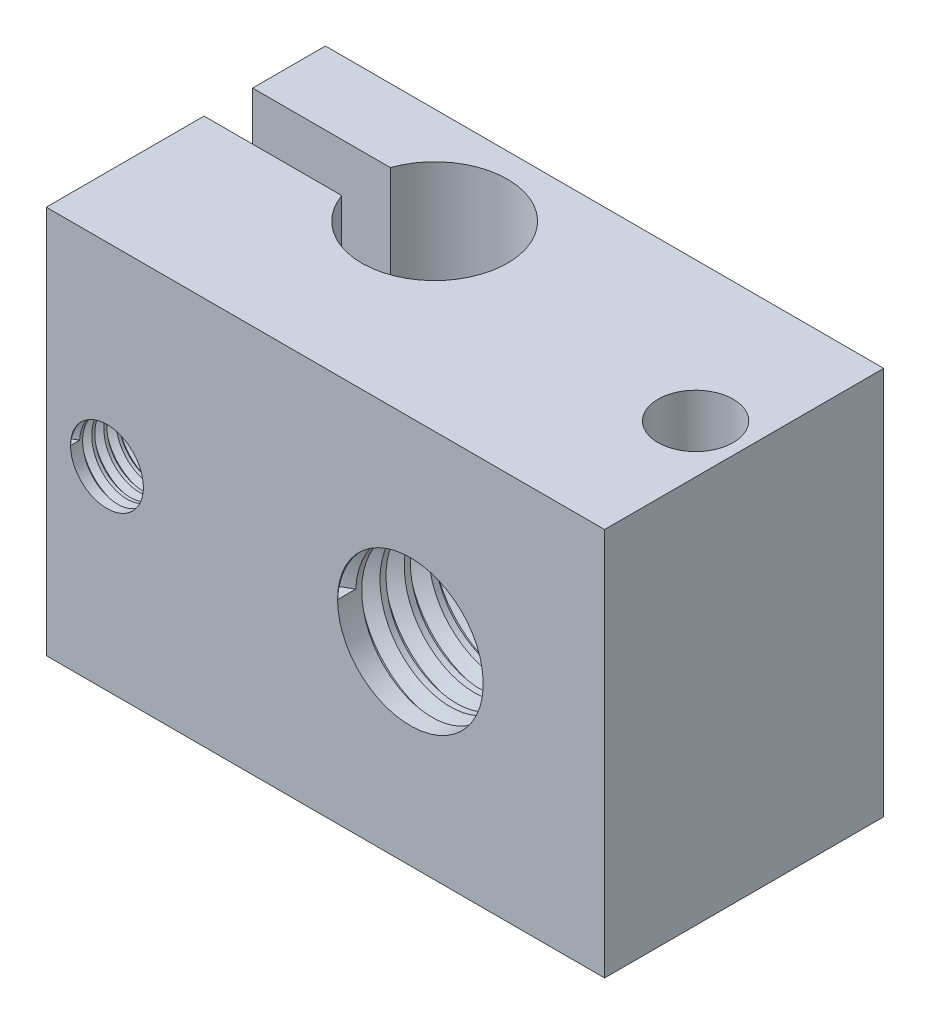
SolidWorks part; units mm, degrees
material "6061 Alloy"
ref_plane "Front Plane" through (0, 0, 0) normal (0, 0, 1) x (1, 0, 0)
ref_plane "Top Plane" through (0, 0, 0) normal (0, 1, 0) x (1, 0, 0)
ref_plane "Right Plane" through (0, 0, 0) normal (1, 0, 0) x (0, 0, -1)
sketch "Sketch1" plane through (0, 0, 0) normal (0, 0, 1) x (1, 0, 0)
  line L1 (-7, 7.0968) -> (16, 7.0968)
  line L2 (-7, 7.0968) -> (-7, -8.9032)
  line L3 (-7, -8.9032) -> (16, -8.9032)
  line L4 (16, 7.0968) -> (16, -8.9032)
  circle A0 centre (8, -0.9032) radius 3
  circle A1 centre (-4.5, -0.9032) radius 1.5
  dimension "D7" = 6
  dimension "D8" = 3
  dimension "D1" = 16
  dimension "D2" = 23
  dimension "D3" = 20.5
  dimension "D4" = 8
  dimension "D5" = 8
  dimension "D6" = 8
extrude "Boss-Extrude1" add sketch "Sketch1" along normal blind 11.5 contours L1 L4 L3 L2 | A1 | A0
sketch "Sketch10" plane through (0, -8.9032, 0) normal (0, -1, 0) x (1, 0, 0)
  line L0 (16, 11.5) -> (16, 0) construction
  line L1 (-7, 0) -> (16, 0) construction
  line L2 (-1.5, 4) -> (-7, 4) construction
  line L3 (-7, 11.5) -> (-7, 0) construction
  line L4 (-1.3284, 5) -> (-7, 5)
  line L5 (-1.3284, 3) -> (-7, 3)
  line L6 (-1.5, 5) -> (-7, 5) construction
  line L7 (-1.5, 3) -> (-7, 3) construction
  line L8 (-7, 5) -> (-7, 3)
  arc A0 (-1.3284, 3) -> (-1.3284, 5) centre (1.5, 4) ccw
  circle A1 centre (14, 5.75) radius 1.55
  dimension "D3" = 6
  dimension "D5" = 3.1
  dimension "D1" = 14.5
  dimension "D2" = 4
  dimension "D4" = 2
  dimension "D6" = 5.75
  dimension "D7" = 1
  dimension "D8" = 2
extrude "Cut-Extrude1" cut sketch "Sketch10" against normal through all
sketch "Sketch11" plane through (0, 0, 0) normal (0, 0, -1) x (-1, 0, 0)
  line L0 (-16, 7.0968) -> (-16, -8.9032) construction
  line L1 (7, -8.9032) -> (-16, -8.9032) construction
  circle A0 centre (-14, -0.9032) radius 1.5
  dimension "D3" = 3
  dimension "D1" = 2
  dimension "D2" = 8
extrude "Cut-Extrude2" cut sketch "Sketch11" against normal blind 6.025
thread "Thread1" pitch 0.5 start angle 0, offset 0, length 11.5, pitch 0.5, diameter 3
ref_plane "Plane1" through (-6, -0.9032, 11.5) normal (0, -1, 0) x (-1, 0, 0)
sketch "Thread Profile1" plane through (-6, -0.9032, 11.5) normal (0, -1, 0) x (-1, 0, 0)
  line L0 (0, 0) -> (0, 0.5) construction
  line L1 (0, 0) -> (0.2706, 0.1562)
  line L2 (0.2706, 0.1562) -> (0.2706, 0.2187)
  line L3 (0.2706, 0.2187) -> (0, 0.375)
  line L4 (0.2706, 0.1875) -> (0, 0.1875) construction
  line L11 (0, 0) -> (0, 0.375)
  point P2 (0, 0)
  dimension "Pitch" = 0.5
  dimension "Profile_Angle" = 60
  dimension "Profile_Land" = 0.0625
  dimension "Profile_Height" = 0.2706
thread "Thread2" pitch 1 profile "Thread Profile2" start angle 0, offset 0, length 11.5, pitch 1, diameter 6
ref_plane "Plane2" through (5, -0.9032, 11.5) normal (0, -1, 0) x (-1, 0, 0)
sketch "Thread Profile2" plane through (5, -0.9032, 11.5) normal (0, -1, 0) x (-1, 0, 0)
  line L0 (0, 0) -> (0, 1) construction
  line L1 (0, 0) -> (0.5413, 0.3125)
  line L2 (0.5413, 0.3125) -> (0.5413, 0.4375)
  line L3 (0.5413, 0.4375) -> (0, 0.75)
  line L4 (0.5413, 0.375) -> (0, 0.375) construction
  line L11 (0, 0) -> (0, 0.75)
  point P2 (0, 0)
  dimension "Pitch" = 1
  dimension "Profile_Angle" = 60
  dimension "Profile_Land" = 0.125
  dimension "Profile_Height" = 0.5413
thread "Thread3" pitch 0.5 profile "Thread Profile3" start angle 0, offset 0, length 5.359, pitch 0.5, diameter 3
ref_plane "Plane3" through (15.5, -0.9032, 0) normal (0, -1, 0) x (1, 0, 0)
sketch "Thread Profile3" plane through (15.5, -0.9032, 0) normal (0, -1, 0) x (1, 0, 0)
  line L0 (0, 0) -> (0, 0.5) construction
  line L1 (0, 0) -> (0.2706, 0.1562)
  line L2 (0.2706, 0.1562) -> (0.2706, 0.2187)
  line L3 (0.2706, 0.2187) -> (0, 0.375)
  line L4 (0.2706, 0.1875) -> (0, 0.1875) construction
  line L11 (0, 0) -> (0, 0.375)
  point P2 (0, 0)
  dimension "Pitch" = 0.5
  dimension "Profile_Angle" = 60
  dimension "Profile_Land" = 0.0625
  dimension "Profile_Height" = 0.2706
